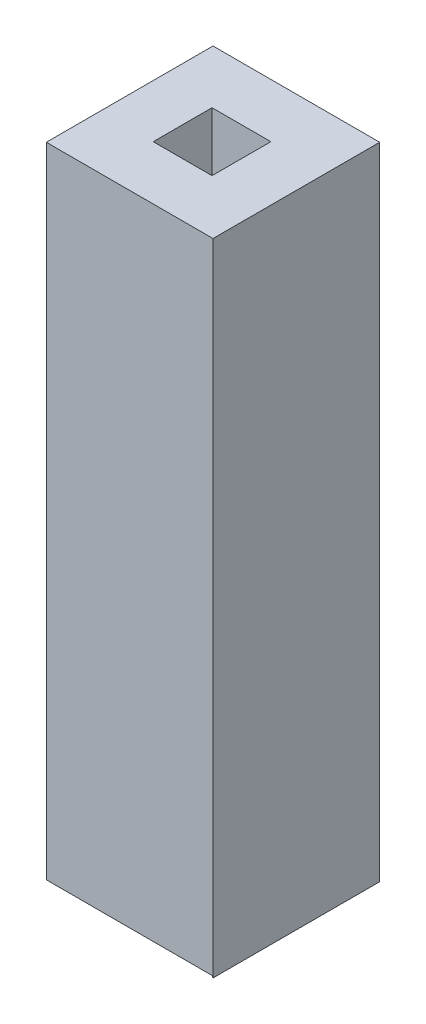
SolidWorks part; units mm, degrees
ref_plane "Front Plane" through (0, 0, 0) normal (0, 0, 1) x (1, 0, 0)
ref_plane "Top Plane" through (0, 0, 0) normal (0, 1, 0) x (1, 0, 0)
ref_plane "Right Plane" through (0, 0, 0) normal (1, 0, 0) x (0, 0, -1)
sketch "Sketch1" plane through (0, 0, 0) normal (0, 1, 0) x (1, 0, 0)
  line L1 (0, 0) -> (2.8333, 0)
  line L2 (0, 0) -> (0, 2.8333)
  line L3 (0, 2.8333) -> (2.8333, 2.8333)
  line L4 (2.8333, 0) -> (2.8333, 2.8333)
  dimension "D1" = 2.8333
other "AlignGroup1"
other "AlignGroup2"
extrude "Boss-Extrude2" add sketch "Sketch1" along normal blind 11
sketch "Sketch2" plane through (0, 0, 0) normal (0, -1, 0) x (-1, 0, 0)
  line L0 (-2.8333, 1.4167) -> (0.1648, 1.4167) construction
  line L1 (-1.9, 0.9167) -> (-0.9, 0.9167)
  line L2 (-1.9, 0.9167) -> (-1.9, 1.9167)
  line L3 (-1.9, 1.9167) -> (-0.9, 1.9167)
  line L4 (-0.9, 0.9167) -> (-0.9, 1.9167)
  line L5 (-1.9, 0.9167) -> (-0.9, 1.9167) construction
  line L6 (-1.9, 1.9167) -> (-0.9, 0.9167) construction
  line L7 (-2.8333, 0) -> (-2.8333, 2.8333) construction
  line L8 (0, 2.8333) -> (0, 0) construction
  point P0 (-1.4, 1.4167)
  dimension "D1" = 1
  dimension "D2" = 0.9
extrude "Cut-Extrude1" cut sketch "Sketch2" against normal blind 11
sketch "Sketch4" plane through (0, 0, 0) normal (0, -1, 0) x (1, 0, 0)
chamfer "Chamfer5" distance 1 angle 60 4 edges at (1.4, 0, -0.9167) (0.9, 0, -1.4167) (1.4, 0, -1.9167) (1.9, 0, -1.4167) first distance on face at (1.4, 0, -1.4167)
